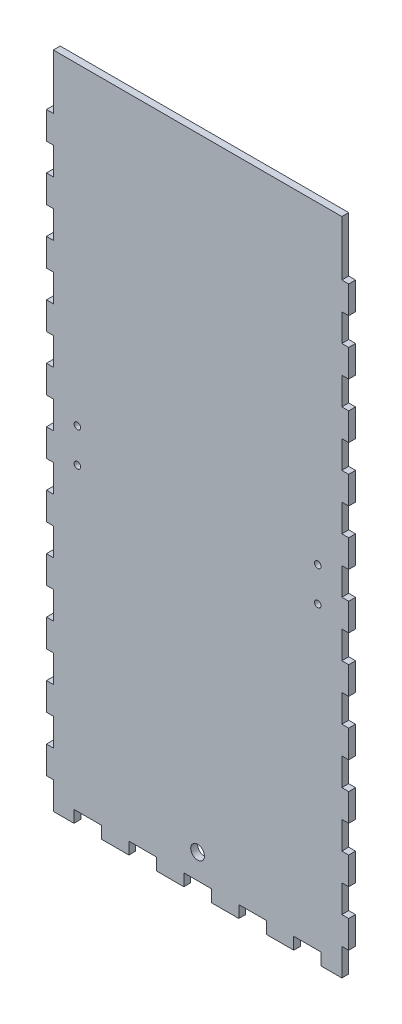
SolidWorks part; units mm, degrees
ref_plane "Front Plane" through (0, 0, 0) normal (0, 0, 1) x (1, 0, 0)
ref_plane "Top Plane" through (0, 0, 0) normal (0, 1, 0) x (1, 0, 0)
ref_plane "Right Plane" through (0, 0, 0) normal (1, 0, 0) x (0, 0, -1)
sketch "Sketch1" plane through (0, 0, 0) normal (0, 0, 1) x (1, 0, 0)
  line L0 (-66.675, 261.112) -> (-66.675, 248.412)
  line L1 (-66.675, 273.812) -> (66.675, 273.812)
  line L2 (-66.675, 273.812) -> (-66.675, 0)
  line L3 (-66.675, 0) -> (66.675, 0)
  line L4 (66.675, 273.812) -> (66.675, 0)
  line L5 (-66.675, 273.812) -> (-69.85, 273.812)
  line L6 (-66.675, 273.812) -> (-66.675, 261.112)
  line L7 (-66.675, 261.112) -> (-69.85, 261.112)
  line L8 (-69.85, 273.812) -> (-69.85, 261.112)
  line L13 (66.675, 273.812) -> (69.85, 273.812)
  line L14 (66.675, 273.812) -> (66.675, 261.112)
  line L15 (66.675, 261.112) -> (69.85, 261.112)
  line L16 (69.85, 273.812) -> (69.85, 261.112)
  line L17 (-66.675, 261.112) -> (-69.85, 261.112)
  line L18 (-69.85, 261.112) -> (-69.85, 248.412)
  line L19 (-66.675, 248.412) -> (-69.85, 248.412)
  line L20 (66.675, 261.112) -> (66.675, 248.412)
  line L21 (66.675, 261.112) -> (69.85, 261.112)
  line L22 (69.85, 261.112) -> (69.85, 248.412)
  line L23 (66.675, 248.412) -> (69.85, 248.412)
  line L24 (-66.675, 248.412) -> (-66.675, 235.712)
  line L25 (-66.675, 248.412) -> (-69.85, 248.412)
  line L26 (-69.85, 248.412) -> (-69.85, 235.712)
  line L27 (-66.675, 235.712) -> (-69.85, 235.712)
  line L28 (66.675, 248.412) -> (66.675, 235.712)
  line L29 (66.675, 248.412) -> (69.85, 248.412)
  line L30 (69.85, 248.412) -> (69.85, 235.712)
  line L31 (66.675, 235.712) -> (69.85, 235.712)
  line L32 (-66.675, 235.712) -> (-66.675, 223.012)
  line L33 (-66.675, 235.712) -> (-69.85, 235.712)
  line L34 (-69.85, 235.712) -> (-69.85, 223.012)
  line L35 (-66.675, 223.012) -> (-69.85, 223.012)
  line L36 (66.675, 235.712) -> (66.675, 223.012)
  line L37 (66.675, 235.712) -> (69.85, 235.712)
  line L38 (69.85, 235.712) -> (69.85, 223.012)
  line L39 (66.675, 223.012) -> (69.85, 223.012)
  line L40 (-66.675, 223.012) -> (-66.675, 210.312)
  line L41 (-66.675, 223.012) -> (-69.85, 223.012)
  line L42 (-69.85, 223.012) -> (-69.85, 210.312)
  line L43 (-66.675, 210.312) -> (-69.85, 210.312)
  line L44 (66.675, 223.012) -> (66.675, 210.312)
  line L45 (66.675, 223.012) -> (69.85, 223.012)
  line L46 (69.85, 223.012) -> (69.85, 210.312)
  line L47 (66.675, 210.312) -> (69.85, 210.312)
  line L48 (-66.675, 210.312) -> (-66.675, 197.612)
  line L49 (-66.675, 210.312) -> (-69.85, 210.312)
  line L50 (-69.85, 210.312) -> (-69.85, 197.612)
  line L51 (-66.675, 197.612) -> (-69.85, 197.612)
  line L52 (66.675, 210.312) -> (66.675, 197.612)
  line L53 (66.675, 210.312) -> (69.85, 210.312)
  line L54 (69.85, 210.312) -> (69.85, 197.612)
  line L55 (66.675, 197.612) -> (69.85, 197.612)
  line L56 (-66.675, 197.612) -> (-66.675, 184.912)
  line L57 (-66.675, 197.612) -> (-69.85, 197.612)
  line L58 (-69.85, 197.612) -> (-69.85, 184.912)
  line L59 (-66.675, 184.912) -> (-69.85, 184.912)
  line L60 (66.675, 197.612) -> (66.675, 184.912)
  line L61 (66.675, 197.612) -> (69.85, 197.612)
  line L62 (69.85, 197.612) -> (69.85, 184.912)
  line L63 (66.675, 184.912) -> (69.85, 184.912)
  line L64 (-66.675, 184.912) -> (-66.675, 172.212)
  line L65 (-66.675, 184.912) -> (-69.85, 184.912)
  line L66 (-69.85, 184.912) -> (-69.85, 172.212)
  line L67 (-66.675, 172.212) -> (-69.85, 172.212)
  line L68 (66.675, 184.912) -> (66.675, 172.212)
  line L69 (66.675, 184.912) -> (69.85, 184.912)
  line L70 (69.85, 184.912) -> (69.85, 172.212)
  line L71 (66.675, 172.212) -> (69.85, 172.212)
  line L72 (-66.675, 172.212) -> (-66.675, 159.512)
  line L73 (-66.675, 172.212) -> (-69.85, 172.212)
  line L74 (-69.85, 172.212) -> (-69.85, 159.512)
  line L75 (-66.675, 159.512) -> (-69.85, 159.512)
  line L76 (66.675, 172.212) -> (66.675, 159.512)
  line L77 (66.675, 172.212) -> (69.85, 172.212)
  line L78 (69.85, 172.212) -> (69.85, 159.512)
  line L79 (66.675, 159.512) -> (69.85, 159.512)
  line L80 (-66.675, 159.512) -> (-66.675, 146.812)
  line L81 (-66.675, 159.512) -> (-69.85, 159.512)
  line L82 (-69.85, 159.512) -> (-69.85, 146.812)
  line L83 (-66.675, 146.812) -> (-69.85, 146.812)
  line L84 (66.675, 159.512) -> (66.675, 146.812)
  line L85 (66.675, 159.512) -> (69.85, 159.512)
  line L86 (69.85, 159.512) -> (69.85, 146.812)
  line L87 (66.675, 146.812) -> (69.85, 146.812)
  line L88 (-66.675, 146.812) -> (-66.675, 134.112)
  line L89 (-66.675, 146.812) -> (-69.85, 146.812)
  line L90 (-69.85, 146.812) -> (-69.85, 134.112)
  line L91 (-66.675, 134.112) -> (-69.85, 134.112)
  line L92 (66.675, 146.812) -> (66.675, 134.112)
  line L93 (66.675, 146.812) -> (69.85, 146.812)
  line L94 (69.85, 146.812) -> (69.85, 134.112)
  line L95 (66.675, 134.112) -> (69.85, 134.112)
  line L96 (-66.675, 134.112) -> (-66.675, 121.412)
  line L97 (-66.675, 134.112) -> (-69.85, 134.112)
  line L98 (-69.85, 134.112) -> (-69.85, 121.412)
  line L99 (-66.675, 121.412) -> (-69.85, 121.412)
  line L100 (66.675, 134.112) -> (66.675, 121.412)
  line L101 (66.675, 134.112) -> (69.85, 134.112)
  line L102 (69.85, 134.112) -> (69.85, 121.412)
  line L103 (66.675, 121.412) -> (69.85, 121.412)
  line L104 (-66.675, 121.412) -> (-66.675, 108.712)
  line L105 (-66.675, 121.412) -> (-69.85, 121.412)
  line L106 (-69.85, 121.412) -> (-69.85, 108.712)
  line L107 (-66.675, 108.712) -> (-69.85, 108.712)
  line L108 (66.675, 121.412) -> (66.675, 108.712)
  line L109 (66.675, 121.412) -> (69.85, 121.412)
  line L110 (69.85, 121.412) -> (69.85, 108.712)
  line L111 (66.675, 108.712) -> (69.85, 108.712)
  line L112 (-66.675, 108.712) -> (-66.675, 96.012)
  line L113 (-66.675, 108.712) -> (-69.85, 108.712)
  line L114 (-69.85, 108.712) -> (-69.85, 96.012)
  line L115 (-66.675, 96.012) -> (-69.85, 96.012)
  line L116 (66.675, 108.712) -> (66.675, 96.012)
  line L117 (66.675, 108.712) -> (69.85, 108.712)
  line L118 (69.85, 108.712) -> (69.85, 96.012)
  line L119 (66.675, 96.012) -> (69.85, 96.012)
  line L120 (-66.675, 96.012) -> (-66.675, 83.312)
  line L121 (-66.675, 96.012) -> (-69.85, 96.012)
  line L122 (-69.85, 96.012) -> (-69.85, 83.312)
  line L123 (-66.675, 83.312) -> (-69.85, 83.312)
  line L124 (66.675, 96.012) -> (66.675, 83.312)
  line L125 (66.675, 96.012) -> (69.85, 96.012)
  line L126 (69.85, 96.012) -> (69.85, 83.312)
  line L127 (66.675, 83.312) -> (69.85, 83.312)
  line L128 (-66.675, 83.312) -> (-66.675, 70.612)
  line L129 (-66.675, 83.312) -> (-69.85, 83.312)
  line L130 (-69.85, 83.312) -> (-69.85, 70.612)
  line L131 (-66.675, 70.612) -> (-69.85, 70.612)
  line L132 (66.675, 83.312) -> (66.675, 70.612)
  line L133 (66.675, 83.312) -> (69.85, 83.312)
  line L134 (69.85, 83.312) -> (69.85, 70.612)
  line L135 (66.675, 70.612) -> (69.85, 70.612)
  line L136 (-66.675, 70.612) -> (-66.675, 57.912)
  line L137 (-66.675, 70.612) -> (-69.85, 70.612)
  line L138 (-69.85, 70.612) -> (-69.85, 57.912)
  line L139 (-66.675, 57.912) -> (-69.85, 57.912)
  line L140 (66.675, 70.612) -> (66.675, 57.912)
  line L141 (66.675, 70.612) -> (69.85, 70.612)
  line L142 (69.85, 70.612) -> (69.85, 57.912)
  line L143 (66.675, 57.912) -> (69.85, 57.912)
  line L144 (-66.675, 57.912) -> (-66.675, 45.212)
  line L145 (-66.675, 57.912) -> (-69.85, 57.912)
  line L146 (-69.85, 57.912) -> (-69.85, 45.212)
  line L147 (-66.675, 45.212) -> (-69.85, 45.212)
  line L148 (66.675, 57.912) -> (66.675, 45.212)
  line L149 (66.675, 57.912) -> (69.85, 57.912)
  line L150 (69.85, 57.912) -> (69.85, 45.212)
  line L151 (66.675, 45.212) -> (69.85, 45.212)
  line L152 (-66.675, 45.212) -> (-66.675, 32.512)
  line L153 (-66.675, 45.212) -> (-69.85, 45.212)
  line L154 (-69.85, 45.212) -> (-69.85, 32.512)
  line L155 (-66.675, 32.512) -> (-69.85, 32.512)
  line L156 (66.675, 45.212) -> (66.675, 32.512)
  line L157 (66.675, 45.212) -> (69.85, 45.212)
  line L158 (69.85, 45.212) -> (69.85, 32.512)
  line L159 (66.675, 32.512) -> (69.85, 32.512)
  line L160 (-66.675, 32.512) -> (-66.675, 19.812)
  line L161 (-66.675, 32.512) -> (-69.85, 32.512)
  line L162 (-69.85, 32.512) -> (-69.85, 19.812)
  line L163 (-66.675, 19.812) -> (-69.85, 19.812)
  line L164 (66.675, 32.512) -> (66.675, 19.812)
  line L165 (66.675, 32.512) -> (69.85, 32.512)
  line L166 (69.85, 32.512) -> (69.85, 19.812)
  line L167 (66.675, 19.812) -> (69.85, 19.812)
  line L168 (-66.675, 19.812) -> (-66.675, 7.112)
  line L169 (-66.675, 19.812) -> (-69.85, 19.812)
  line L170 (-69.85, 19.812) -> (-69.85, 7.112)
  line L171 (-66.675, 7.112) -> (-69.85, 7.112)
  line L172 (66.675, 19.812) -> (66.675, 7.112)
  line L173 (66.675, 19.812) -> (69.85, 19.812)
  line L174 (69.85, 19.812) -> (69.85, 7.112)
  line L175 (66.675, 7.112) -> (69.85, 7.112)
  line L176 (-66.675, 7.112) -> (-66.675, -5.588)
  line L177 (-66.675, 7.112) -> (-69.85, 7.112)
  line L178 (-69.85, 7.112) -> (-69.85, -5.588)
  line L179 (-66.675, -5.588) -> (-69.85, -5.588)
  line L180 (66.675, 7.112) -> (66.675, -5.588)
  line L181 (66.675, 7.112) -> (69.85, 7.112)
  line L182 (69.85, 7.112) -> (69.85, -5.588)
  line L183 (66.675, -5.588) -> (69.85, -5.588)
  line L184 (-57.15, 0) -> (-57.15, -5.588)
  line L185 (-69.85, 0) -> (-57.15, 0)
  line L186 (-69.85, 0) -> (-69.85, -5.588)
  line L187 (-69.85, -5.588) -> (-57.15, -5.588)
  line L188 (-57.15, 0) -> (-57.15, -5.588)
  line L189 (-57.15, 0) -> (-44.45, 0)
  line L190 (-44.45, 0) -> (-44.45, -5.588)
  line L191 (-57.15, -5.588) -> (-44.45, -5.588)
  line L192 (-44.45, 0) -> (-44.45, -5.588)
  line L193 (-44.45, 0) -> (-31.75, 0)
  line L194 (-31.75, 0) -> (-31.75, -5.588)
  line L195 (-44.45, -5.588) -> (-31.75, -5.588)
  line L196 (-31.75, 0) -> (-31.75, -5.588)
  line L197 (-31.75, 0) -> (-19.05, 0)
  line L198 (-19.05, 0) -> (-19.05, -5.588)
  line L199 (-31.75, -5.588) -> (-19.05, -5.588)
  line L200 (-19.05, 0) -> (-19.05, -5.588)
  line L201 (-19.05, 0) -> (-6.35, 0)
  line L202 (-6.35, 0) -> (-6.35, -5.588)
  line L203 (-19.05, -5.588) -> (-6.35, -5.588)
  line L204 (-6.35, 0) -> (-6.35, -5.588)
  line L205 (-6.35, 0) -> (6.35, 0)
  line L206 (6.35, 0) -> (6.35, -5.588)
  line L207 (-6.35, -5.588) -> (6.35, -5.588)
  line L208 (6.35, 0) -> (6.35, -5.588)
  line L209 (6.35, 0) -> (19.05, 0)
  line L210 (19.05, 0) -> (19.05, -5.588)
  line L211 (6.35, -5.588) -> (19.05, -5.588)
  line L212 (19.05, 0) -> (19.05, -5.588)
  line L213 (19.05, 0) -> (31.75, 0)
  line L214 (31.75, 0) -> (31.75, -5.588)
  line L215 (19.05, -5.588) -> (31.75, -5.588)
  line L216 (31.75, 0) -> (31.75, -5.588)
  line L217 (31.75, 0) -> (44.45, 0)
  line L218 (44.45, 0) -> (44.45, -5.588)
  line L219 (31.75, -5.588) -> (44.45, -5.588)
  line L220 (44.45, 0) -> (44.45, -5.588)
  line L221 (44.45, 0) -> (57.15, 0)
  line L222 (57.15, 0) -> (57.15, -5.588)
  line L223 (44.45, -5.588) -> (57.15, -5.588)
  line L224 (57.15, 0) -> (57.15, -5.588)
  line L225 (57.15, 0) -> (69.85, 0)
  line L226 (69.85, 0) -> (69.85, -5.588)
  line L227 (57.15, -5.588) -> (69.85, -5.588)
  point P4 (0, 0)
  dimension "D1" = 133.35
  dimension "D2" = 273.812
  dimension "D3" = 139.7
  dimension "D6" = 279.4
  dimension "D7" = 12.7
  dimension "D8" = 12.7
  dimension "D4" = 22
  dimension "D5" = 11
extrude "Boss-Extrude1" add sketch "Sketch1" along normal blind 3.175 contours L4 L1 L2 L0 L3 | L171 L2 L163 L170 | L155 L2 L147 L154 | L139 L2 L131 L138 | L123 L2 L115 L122 | L176 L187 L184 L3 | L190 L195 L194 L3 | L198 L203 L202 L3 | L206 L211 L210 L3 | L214 L219 L218 L3 | L222 L227 L180 L3 | L4 L175 L174 L167 | L4 L159 L158 L151 | L4 L143 L142 L135 | L4 L127 L126 L119 | L4 L111 L110 L103 | L107 L2 L99 L106 | L91 L2 L83 L90 | L75 L2 L67 L74 | L59 L2 L51 L58 | L43 L2 L35 L42 | L27 L2 L19 L26 | L5 L8 L7 L2 | L4 L95 L94 L87 | L4 L79 L78 L71 | L4 L63 L62 L55 | L4 L47 L46 L39 | L4 L31 L30 L23 | L16 L13 L4 L15 region at (0, 136.906, 0) region at (-68.2625, 267.462, 0) region at (-68.2625, 242.062, 0) region at (68.2625, 267.462, 0) region at (-68.2625, 216.662, 0) region at (68.2625, 242.062, 0) region at (-68.2625, 191.262, 0) region at (68.2625, 216.662, 0) region at (-68.2625, 165.862, 0) region at (68.2625, 191.262, 0) region at (-68.2625, 140.462, 0) region at (68.2625, 165.862, 0) region at (-68.2625, 115.062, 0) region at (68.2625, 140.462, 0) region at (-68.2625, 89.662, 0) region at (68.2625, 115.062, 0) region at (-68.2625, 64.262, 0) region at (68.2625, 89.662, 0) region at (-68.2625, 38.862, 0) region at (68.2625, 64.262, 0) region at (-68.2625, 13.462, 0) region at (68.2625, 38.862, 0) region at (-61.9125, -2.794, 0) region at (68.2625, 13.462, 0) region at (-38.1, -2.794, 0) region at (61.9125, -2.794, 0) region at (-12.7, -2.794, 0) region at (38.1, -2.794, 0) region at (12.7, -2.794, 0)
sketch "Sketch2" plane through (0, 0, 3.175) normal (0, 0, 1) x (1, 0, 0)
  circle A0 centre (0, 11.43) radius 3.175
  dimension "D2" = 6.35
  dimension "D1" = 11.43
extrude "Cut-Extrude1" cut sketch "Sketch2" against normal through all
sketch "Sketch3" plane through (0, 0, 3.175) normal (0, 0, 1) x (1, 0, 0)
  line L0 (-55.5625, 154.305) -> (-55.5625, 138.557) construction
  line L1 (55.5625, 154.305) -> (55.5625, 138.557) construction
  line L2 (-55.5625, 146.431) -> (55.5625, 146.431) construction
  line L3 (-57.15, 0) -> (-44.45, 0) construction
  line L5 (-69.85, 146.812) -> (-69.85, 134.112) construction
  circle A0 centre (-55.5625, 154.305) radius 1.5
  circle A1 centre (-55.5625, 138.557) radius 1.5
  circle A2 centre (55.5625, 154.305) radius 1.5
  circle A3 centre (55.5625, 138.557) radius 1.5
  point P10 (0, 146.431)
  dimension "D2" = 3
  dimension "D3" = 138.557
  dimension "D4" = 14.2875
  dimension "D1" = 15.748
extrude "Cut-Extrude2" cut sketch "Sketch3" against normal through all
sketch "Sketch4" plane through (0, 0, 3.175) normal (0, 0, 1) x (1, 0, 0)
  line L0 (-69.85, 273.812) -> (69.85, 273.812) construction
  line L1 (-66.675, 273.812) -> (66.675, 273.812)
  line L2 (-66.675, 273.812) -> (-66.675, 299.212)
  line L3 (-66.675, 299.212) -> (66.675, 299.212)
  line L4 (66.675, 273.812) -> (66.675, 299.212)
  point P6 (0, 0)
  point P8 (0, 0)
  dimension "D1" = 25.4
extrude "Boss-Extrude2" add sketch "Sketch4" against normal up to surface (3.175 mm away) up to face at (-54.0625, 138.557, 0)
equation "\"bottomThickness\"= .220in"
equation "\"wallThickness\"= .125in"
equation "\"D3@Sketch1\"=2*\"wallThickness\"+5.25"
equation "\"D6@Sketch1\"=\"bottomThickness\"+10.78"
equation "\"D7@Sketch1\"=\"D6@Sketch1\"/\"D4@Sketch1\""
equation "\"D8@Sketch1\"=\"D3@Sketch1\"/\"D5@Sketch1\""
equation "\"D1@Boss-Extrude1\"=\"wallThickness\""
